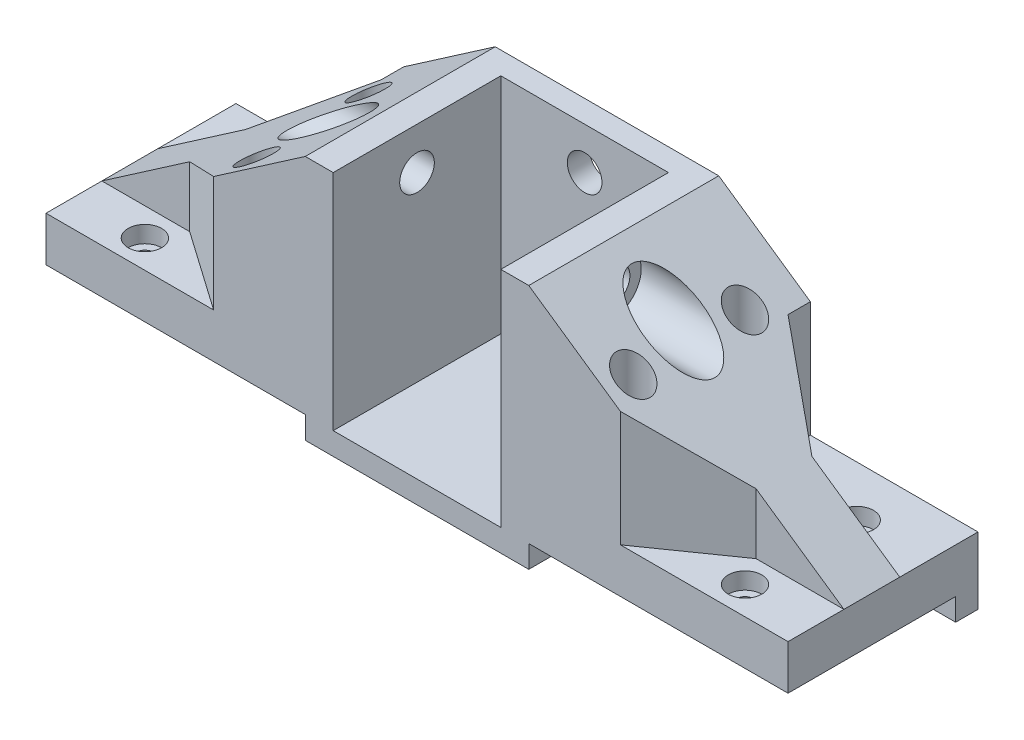
SolidWorks part; units mm, degrees
ref_plane "Front Plane" through (0, 0, 0) normal (0, 0, 1) x (1, 0, 0)
ref_plane "Top Plane" through (0, 0, 0) normal (0, 1, 0) x (1, 0, 0)
ref_plane "Right Plane" through (0, 0, 0) normal (1, 0, 0) x (0, 0, -1)
sketch "Sketch1" plane through (0, 0, 0) normal (0, 0, 1) x (1, 0, 0)
  line L1 (-66.4, 22) -> (66.4, 22)
  line L2 (-66.4, 22) -> (-66.4, -22)
  line L3 (-66.4, -22) -> (66.4, -22)
  line L4 (66.4, 22) -> (66.4, -22)
  line L5 (-66.4, 22) -> (66.4, -22) construction
  line L6 (-66.4, -22) -> (66.4, 22) construction
  point P0 (0, 0)
extrude "Boss-Extrude1" add sketch "Sketch1" along normal blind 4
sketch "Sketch2" plane through (0, 0, 4) normal (0, 0, 1) x (1, 0, 0)
  line L0 (-15, 0) -> (15, 0) construction
  line L1 (-15, -22) -> (-15, -18) construction
  line L2 (-66.4, -22) -> (66.4, -22) construction
  line L3 (-15, -18) -> (15, -18)
  line L4 (15, -18) -> (15, 22)
  line L5 (66.4, 22) -> (-66.4, 22) construction
  line L6 (-15, -18) -> (-15, 22)
  line L7 (-15, 22) -> (-20, 22)
  line L8 (15, 22) -> (20, 22)
  line L9 (20, 22) -> (20, -22)
  line L10 (20, -22) -> (-20, -22)
  line L11 (-20, -22) -> (-20, 22)
  line L12 (-66.4, -22) -> (-66.4, -18) construction
  line L13 (-66.4, 22) -> (-66.4, -22) construction
  line L14 (-66.4, -18) -> (-20, -18)
  line L15 (-66.4, -18) -> (-66.4, -10)
  line L16 (-66.4, -10) -> (-20, -10)
  line L17 (20, -10) -> (66.4, -10)
  line L18 (66.4, -22) -> (66.4, 22) construction
  line L19 (66.4, -10) -> (66.4, -18)
  line L20 (66.4, -18) -> (20, -18)
  point P3 (0, 0)
  line M3 (66.4, -22) -> (66.4, 22)
  line M4 (66.4, 22) -> (-66.4, 22)
  line M5 (-66.4, 22) -> (-66.4, -22)
  line M6 (-66.4, -22) -> (66.4, -22)
extrude "Boss-Extrude2" add sketch "Sketch2" along normal blind 30 contours L16 L14 L11 M5 | L11 L9 L4 L3 L6 M6 M4 | L20 L17 L9 M3 region at (0, -18.5946, 4) region at (-43.2, -14, 4) region at (43.2, -14, 4)
ref_plane "Plane1" through (0, 0, 19) normal (0, 0, 1) x (1, 0, 0)
ref_plane "Plane2" through (0, -10, 0) normal (0, 1, 0) x (1, 0, 0)
ref_plane "Plane3" through (20, 0, 0) normal (1, 0, 0) x (0, 0, -1)
ref_plane "Plane4" through (-20, 0, 0) normal (-1, 0, 0) x (0, 0, 1)
sketch "Sketch5" plane through (0, 0, 19) normal (0, 0, 1) x (1, 0, 0)
  line L3 (0, 16.0797) -> (0, -11.7191) construction
  line L7 (20, -10) -> (66.4, -10)
  line L14 (66.4, -10) -> (20, 22)
  line L15 (20, 22) -> (20, -10)
  line L16 (-20, 22) -> (-20, -10)
  line L17 (-66.4, -10) -> (-20, 22)
  line L18 (-20, -10) -> (-66.4, -10)
extrude "Boss-Extrude3" add sketch "Sketch5" along normal mid plane 30
sketch "Sketch6" plane through (-15, 0, 0) normal (1, 0, 0) x (0, 0, -1)
  line L0 (-34, 22) -> (-34, 14.5) construction
  line L1 (-34, -18) -> (-34, 22) construction
  line L2 (-34, 14.5) -> (-4, 14.5) construction
  line L3 (-4, -18) -> (-4, 22) construction
  line L4 (-19, 14.5) -> (-19, 18.925) construction
  circle A0 centre (-19, 14.5) radius 3.1
extrude "Cut-Extrude3" cut sketch "Sketch6" against normal through all both and the other way through all
sketch "Sketch8" plane through (20, 0, 0) normal (1, 0, 0) x (0, 0, -1)
  circle A0 centre (-19, 14.5) radius 5.125
extrude "Cut-Extrude5" cut sketch "Sketch8" along normal through all
sketch "Sketch9" plane through (-20, 0, 0) normal (-1, 0, 0) x (0, 0, 1)
  circle A0 centre (19, 14.5) radius 5.125
extrude "Cut-Extrude6" cut sketch "Sketch9" along normal through all
sketch "Sketch7" plane through (0, -10, 0) normal (0, 1, 0) x (1, 0, 0)
  line L0 (0, 19.9065) -> (0, -47.3008) construction
  line L2 (66.4, -34) -> (66.4, -4) construction
  line L3 (50.6815, -14) -> (66.4, -14)
  line L4 (66.4, -19) -> (21, -19) construction
  line L7 (33.7, -9) -> (33.7, -29) construction
  line L8 (33.7, -29) -> (53.7, -29) construction
  line L9 (53.7, -9) -> (53.7, -29) construction
  line L10 (33.7, -9) -> (53.7, -29) construction
  line L11 (33.7, -29) -> (53.7, -9) construction
  line L15 (66.4, -34) -> (66.4, -24)
  line L16 (66.4, -34) -> (36.4, -34)
  line L17 (66.4, -34) -> (20, -34) construction
  line L20 (-66.4, -24) -> (-23.5182, -24) construction
  line L21 (-33.7, -29) -> (-53.7, -9) construction
  line L26 (-33.7, -9) -> (-53.7, -29) construction
  line L27 (-53.7, -9) -> (-53.7, -29) construction
  line L36 (66.4, -24) -> (23.5182, -24) construction
  line L38 (36.4, -34) -> (50.6815, -24)
  line L39 (50.6815, -24) -> (66.4, -24)
  line L40 (36.4, -4) -> (50.6815, -14)
  line L41 (66.4, -4) -> (36.4, -4)
  line L42 (66.4, -4) -> (66.4, -14)
  line L43 (-33.7, -29) -> (-53.7, -29) construction
  line L44 (-33.7, -9) -> (-33.7, -29) construction
  line L45 (-66.4, -19) -> (-21, -19) construction
  line L46 (-66.4, -4) -> (-66.4, -14)
  line L47 (-66.4, -4) -> (-36.4, -4)
  line L48 (-36.4, -4) -> (-50.6815, -14)
  line L49 (-50.6815, -24) -> (-66.4, -24)
  line L50 (-36.4, -34) -> (-50.6815, -24)
  line L51 (-66.4, -34) -> (-36.4, -34)
  line L52 (-66.4, -34) -> (-66.4, -24)
  line L53 (-50.6815, -14) -> (-66.4, -14)
  point P11 (43.7, -19)
  point P38 (-43.7, -19)
  dimension "D1" = 10
extrude "Cut-Extrude4" cut sketch "Sketch7" along normal through all
sketch "Sketch3" plane through (0, -10, 0) normal (0, 1, 0) x (1, 0, 0)
  line L0 (-66.4, -19) -> (-21, -19) construction
  line L2 (0, -4) -> (0, -34) construction
  line L3 (-53.7, -9) -> (-33.7, -9) construction
  line L4 (-53.7, -9) -> (-53.7, -29) construction
  line L5 (-53.7, -29) -> (-33.7, -29) construction
  line L6 (-33.7, -9) -> (-33.7, -29) construction
  line L7 (-53.7, -9) -> (-33.7, -29) construction
  line L8 (-53.7, -29) -> (-33.7, -9) construction
  line L9 (-15, -4) -> (15, -4) construction
  line L10 (-15, -34) -> (15, -34) construction
  line L11 (53.7, -29) -> (33.7, -9) construction
  line L12 (53.7, -9) -> (33.7, -29) construction
  line L13 (33.7, -9) -> (33.7, -29) construction
  line L14 (53.7, -29) -> (33.7, -29) construction
  line L15 (53.7, -9) -> (53.7, -29) construction
  line L16 (53.7, -9) -> (33.7, -9) construction
  line L17 (66.4, -19) -> (21, -19) construction
  circle A0 centre (-53.7, -9) radius 1.6
  circle A1 centre (-33.7, -29) radius 1.6
  circle A2 centre (-33.7, -9) radius 1.6
  circle A3 centre (-53.7, -29) radius 1.6
  circle A4 centre (33.7, -9) radius 1.6
  circle A5 centre (33.7, -29) radius 1.6
  circle A6 centre (53.7, -29) radius 1.6
  circle A7 centre (53.7, -9) radius 1.6
  point P4 (-43.7, -19)
  point P21 (43.7, -19)
extrude "Cut-Extrude1" cut sketch "Sketch3" against normal blind 30
sketch "Sketch4" plane through (0, -10, 0) normal (0, 1, 0) x (1, 0, 0)
  circle A0 centre (-53.7, -9) radius 3
  circle A1 centre (-33.7, -9) radius 3
  circle A2 centre (-33.7, -29) radius 3
  circle A3 centre (-53.7, -29) radius 3
  circle A4 centre (33.7, -9) radius 3
  circle A5 centre (53.7, -9) radius 3
  circle A6 centre (53.7, -29) radius 3
  circle A7 centre (33.7, -29) radius 3
  dimension "D1" = 2
  dimension "D3" = 2
  dimension "D2" = 2
  dimension "D4" = 2
extrude "Cut-Extrude2" cut sketch "Sketch4" against normal blind 3 and the other way through all
sketch "Sketch10" plane through (0, 0, 4) normal (0, 0, 1) x (1, 0, 0)
  line L0 (20, 22) -> (36.4, 10.6897)
  line L1 (36.4, 10.6897) -> (36.4, -10)
  line L2 (36.4, -10) -> (66.4, -10)
  line L3 (66.4, -10) -> (66.4, 22)
  line L4 (66.4, 22) -> (20, 22)
  line L5 (0, 32.6044) -> (0, -12.2279) construction
  line L6 (-66.4, 22) -> (-20, 22)
  line L7 (-66.4, -10) -> (-66.4, 22)
  line L8 (-36.4, -10) -> (-66.4, -10)
  line L9 (-36.4, 10.6897) -> (-36.4, -10)
  line L10 (-20, 22) -> (-36.4, 10.6897)
extrude "Cut-Extrude7" cut sketch "Sketch10" against normal through all
sketch "Sketch11" plane through (0, 0, 4) normal (0, 0, 1) x (1, 0, 0)
  line L0 (0, 22) -> (0, 14.5) construction
  line L1 (15, 22) -> (-15, 22) construction
  circle A0 centre (0, 14.5) radius 3.1
extrude "Cut-Extrude8" cut sketch "Sketch11" against normal through all
